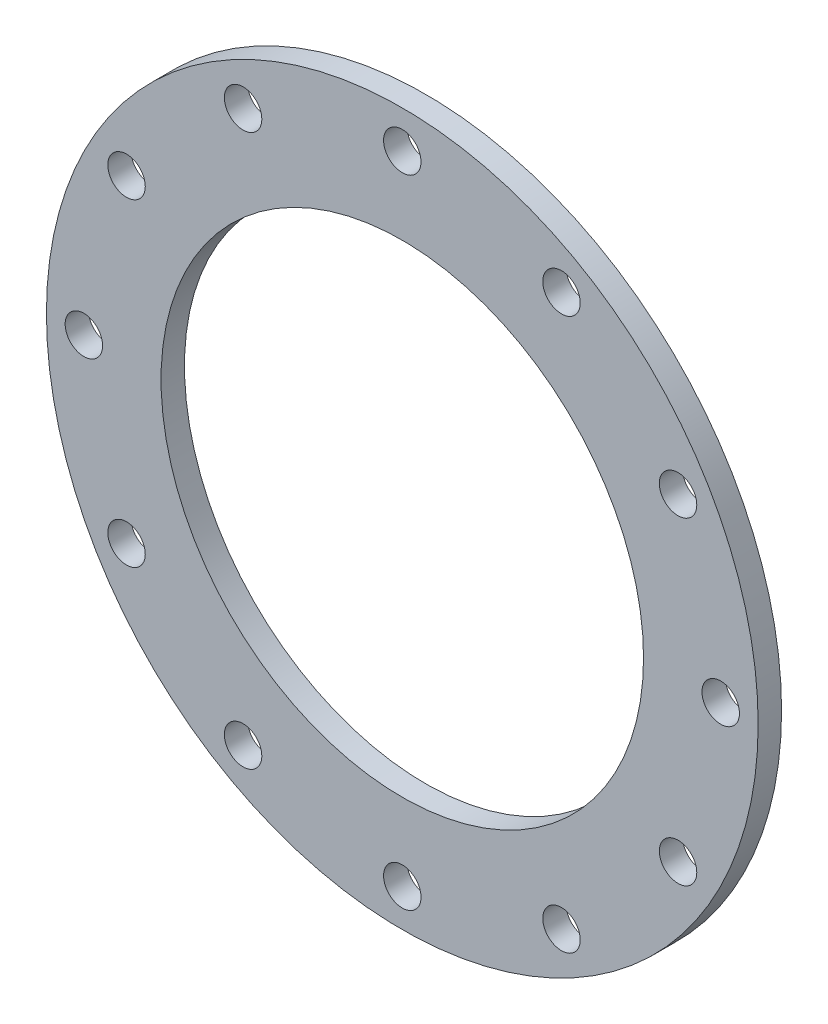
SolidWorks part; units mm, degrees
ref_plane "Front Plane" through (0, 0, 0) normal (0, 0, 1) x (1, 0, 0)
ref_plane "Top Plane" through (0, 0, 0) normal (0, 1, 0) x (1, 0, 0)
ref_plane "Right Plane" through (0, 0, 0) normal (1, 0, 0) x (0, 0, -1)
sketch "Profile Sketch" plane through (0, 0, 0) normal (0, 0, 1) x (1, 0, 0)
  circle A0 centre (0, 0) radius 241.3
  circle A1 centre (0, 0) radius 163.576
  circle A2 centre (0, 0) radius 215.9 construction
  circle A3 centre (0, 215.9) radius 12.7
  circle A4 centre (107.95, 186.9749) radius 12.7
  circle A5 centre (186.9749, 107.95) radius 12.7
  circle A6 centre (215.9, 0) radius 12.7
  circle A7 centre (186.9749, -107.95) radius 12.7
  circle A8 centre (107.95, -186.9749) radius 12.7
  circle A9 centre (0, -215.9) radius 12.7
  circle A10 centre (-107.95, -186.9749) radius 12.7
  circle A11 centre (-186.9749, -107.95) radius 12.7
  circle A12 centre (-215.9, 0) radius 12.7
  circle A13 centre (-186.9749, 107.95) radius 12.7
  circle A14 centre (-107.95, 186.9749) radius 12.7
  point P31 (0, 0)
  dimension "D1" = 327.152
  dimension "D2" = 482.6
  dimension "D3" = 431.8
  dimension "D4" = 25.4
  dimension "D5" = 12
extrude "Boss-Extrude1" add sketch "Profile Sketch" along normal blind 15.875
equation "\"ID\" = 12.88in'RJSALES"
equation "\"BC\"= 17in'RJSALES"
equation "\"OD\"= 19in'RJSALES"
equation "\"HD\"= 1in'RJSALES"
equation "\"T\"= 0.625in'RJSALES"
equation "\"D1@Profile Sketch\" = \"ID\""
equation "\"D2@Profile Sketch\" = \"OD\""
equation "\"D3@Profile Sketch\" = \"BC\""
equation "\"D4@Profile Sketch\" = \"HD\""
equation "\"D1@Boss-Extrude1\"=\"T\""
